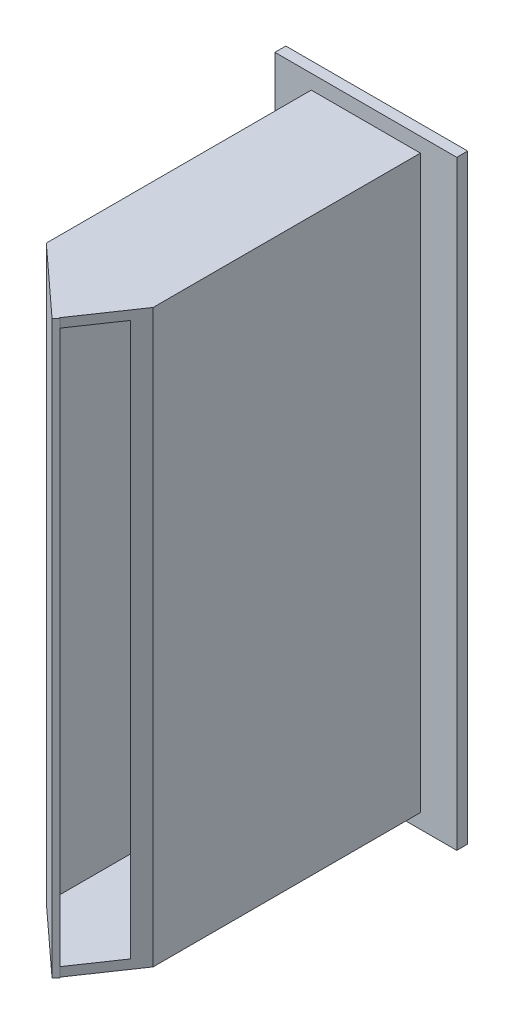
SolidWorks part; units mm, degrees
ref_plane "前视基准面" through (0, 0, 0) normal (0, 0, 1) x (1, 0, 0)
ref_plane "上视基准面" through (0, 0, 0) normal (0, 1, 0) x (1, 0, 0)
ref_plane "右视基准面" through (0, 0, 0) normal (1, 0, 0) x (0, 0, -1)
sketch "草图1" plane through (0, 0, 0) normal (0, 0, 1) x (1, 0, 0)
  line L0 (0, 16.5) -> (10, 16.5) construction
  line L1 (0, 0) -> (10, 0)
  line L2 (0, 0) -> (0, 33)
  line L3 (0, 33) -> (10, 33)
  line L4 (10, 0) -> (10, 33)
  line L5 (2.5, 31.7) -> (7.5, 31.7)
  line L6 (2.5, 31.7) -> (2.5, 1.3)
  line L7 (2.5, 1.3) -> (7.5, 1.3)
  line L8 (7.5, 31.7) -> (7.5, 1.3)
  line L9 (5, 33) -> (5, 0) construction
  dimension "D1" = 33
  dimension "D2" = 10
  dimension "D3" = 5
  dimension "D4" = 30.4
extrude "凸台-拉伸1" add sketch "草图1" along normal blind 0.6
sketch "草图2" plane through (0, 0, 0.6) normal (0, 0, 1) x (1, 0, 0)
  line L0 (7.5, 1.3) -> (7.5, 31.7) construction
  line L1 (2, 32.2) -> (8, 32.2)
  line L2 (2, 32.2) -> (2, 0.8)
  line L3 (2, 0.8) -> (8, 0.8)
  line L4 (8, 32.2) -> (8, 0.8)
  line L5 (2.5, 31.7) -> (2.5, 1.3) construction
  line L6 (7.5, 31.7) -> (2.5, 31.7) construction
  line L7 (2.5, 1.3) -> (7.5, 1.3) construction
  line L9 (2.5, 31.7) -> (7.5, 31.7)
  line L10 (2.5, 31.7) -> (2.5, 1.3)
  line L11 (2.5, 1.3) -> (7.5, 1.3)
  line L12 (7.5, 31.7) -> (7.5, 1.3)
  dimension "D1" = 0.5
  dimension "D2" = 0.5
  dimension "D3" = 0.5
  dimension "D4" = 0.5
extrude "凸台-拉伸2" add sketch "草图2" along normal blind 18
sketch "草图5" plane through (0, 32.2, 0) normal (0, 1, 0) x (1, 0, 0)
  line L0 (2, -15.1659) -> (5.749, -18.6)
  line L1 (2, -18.6) -> (2, -0.6) construction
  line L2 (8, -18.6) -> (2, -18.6) construction
  line L3 (5.749, -18.6) -> (8, -15.2935)
  line L4 (8, -18.6) -> (8, -0.6) construction
  line L5 (2, -15.1659) -> (2, -19.3766)
  line L6 (2, -19.3766) -> (8, -19.3766)
  line L7 (8, -19.3766) -> (8, -15.2935)
  dimension "D1" = 4
extrude "切除-拉伸1" cut sketch "草图5" against normal through all
sketch "草图6" plane through (-6.6413, 0, 7.2502) normal (-0.6755, 0, 0.7374) x (0.7374, 0, 0.6755)
  line L1 (11.7188, 32.2) -> (16.8029, 32.2)
  line L2 (11.7188, 32.2) -> (11.7188, 0.8)
  line L3 (11.7188, 0.8) -> (16.8029, 0.8)
  line L4 (16.8029, 32.2) -> (16.8029, 0.8)
extrude "凸台-拉伸5" add sketch "草图6" against normal blind 0.3
